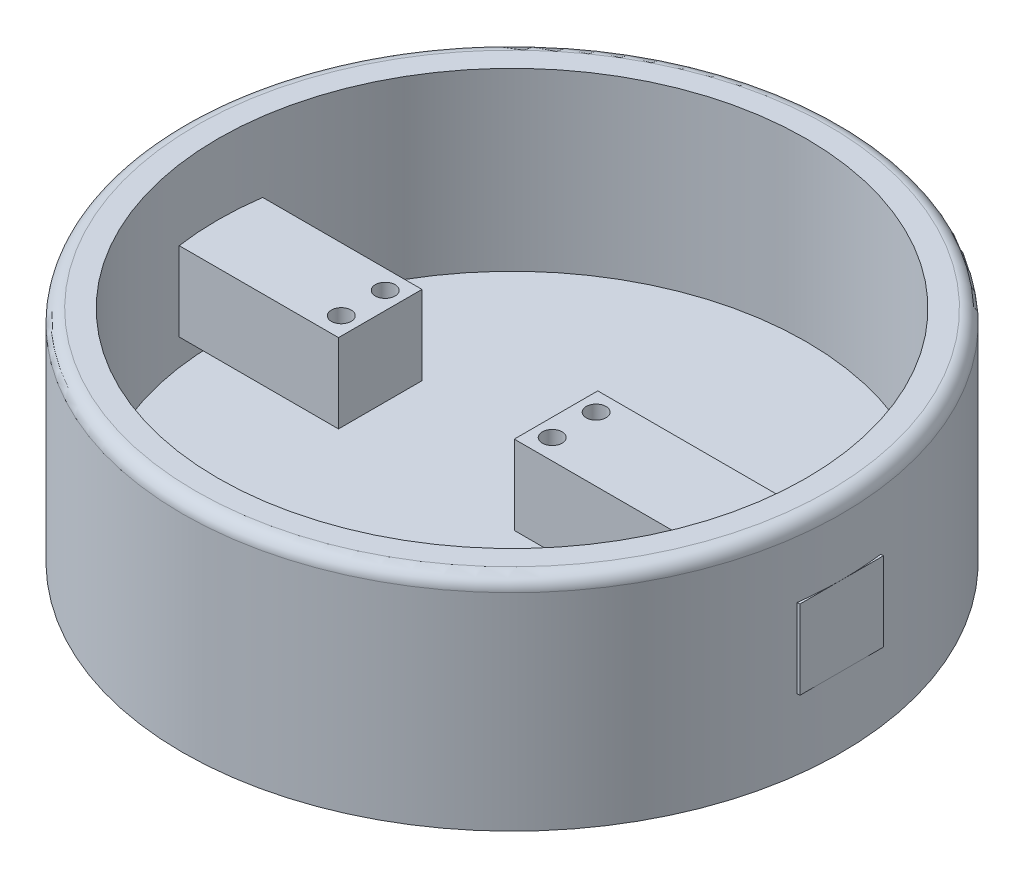
SolidWorks part; units mm, degrees
ref_plane "Front Plane" through (0, 0, 0) normal (0, 0, 1) x (1, 0, 0)
ref_plane "Top Plane" through (0, 0, 0) normal (0, 1, 0) x (1, 0, 0)
ref_plane "Right Plane" through (0, 0, 0) normal (1, 0, 0) x (0, 0, -1)
sketch "Sketch1" plane through (0, 0, 0) normal (0, 1, 0) x (1, 0, 0)
  circle A0 centre (0, 0) radius 75
  circle A1 centre (0, 0) radius 66.9251
  dimension "D1" = 150
  dimension "D2" = 133.8501
extrude "Boss-Extrude3" add sketch "Sketch1" along normal blind 10 contours A0
extrude "Boss-Extrude4" add sketch "Sketch1<4>" along normal blind 50
sketch "Sketch1<4>" plane through (0, 0, 0) normal (0, 1, 0) x (1, 0, 0) same geometry as "Sketch1"
sketch "Sketch2" plane through (0, 50, 0) normal (0, 1, 0) x (1, 0, 0)
  circle A0 centre (0, 0) radius 75 construction
  point P0 (75, 0)
  point P4 (-75, 0)
ref_plane "Plane1" through (75, 50, 0) normal (1, 0, 0) x (0, 0, -1)
sketch "Sketch3" plane through (75, 50, 0) normal (1, 0, 0) x (0, 0, -1)
  line L1 (-9.5, -16) -> (9.5, -16)
  line L2 (-9.5, -16) -> (-9.5, -34)
  line L3 (-9.5, -34) -> (9.5, -34)
  line L4 (9.5, -16) -> (9.5, -34)
  line L5 (-9.5, -16) -> (9.5, -34) construction
  line L6 (-9.5, -34) -> (9.5, -16) construction
  point P0 (0, -25)
  dimension "D1" = 25
  dimension "D2" = 19
  dimension "D3" = 18
extrude "Boss-Extrude5" add sketch "Sketch3" against normal blind 65
ref_plane "Plane2" through (-75, 50, 0) normal (-1, 0, 0) x (0, 0, 1)
sketch "Sketch4" plane through (-75, 50, 0) normal (-1, 0, 0) x (0, 0, 1)
  line L1 (-9.5, -16) -> (9.5, -16)
  line L2 (-9.5, -16) -> (-9.5, -34)
  line L3 (-9.5, -34) -> (9.5, -34)
  line L4 (9.5, -16) -> (9.5, -34)
  line L5 (-9.5, -16) -> (9.5, -34) construction
  line L6 (-9.5, -34) -> (9.5, -16) construction
  point P0 (0, -25)
  dimension "D1" = 25
  dimension "D2" = 19
  dimension "D3" = 18
extrude "Boss-Extrude6" add sketch "Sketch4" against normal blind 45
sketch "Sketch5" plane through (0, 34, 0) normal (0, 1, 0) x (1, 0, 0)
  line L0 (10, 9.5) -> (10, -9.5) construction
  line L1 (-30, -9.5) -> (-30, 9.5) construction
  circle A0 centre (14, 5.1308) radius 2.25
  circle A1 centre (14, -4.8692) radius 2.25
  circle A2 centre (-34, 5.1308) radius 2.25
  circle A3 centre (-34, -4.8692) radius 2.25
  dimension "D1" = 4.5
  dimension "D2" = 4
  dimension "D3" = 10
  dimension "D4" = 4
extrude "Cut-Extrude1" cut sketch "Sketch5" against normal blind 15
fillet "Fillet2" radius 3 1 edges at (0, 50, 75)
